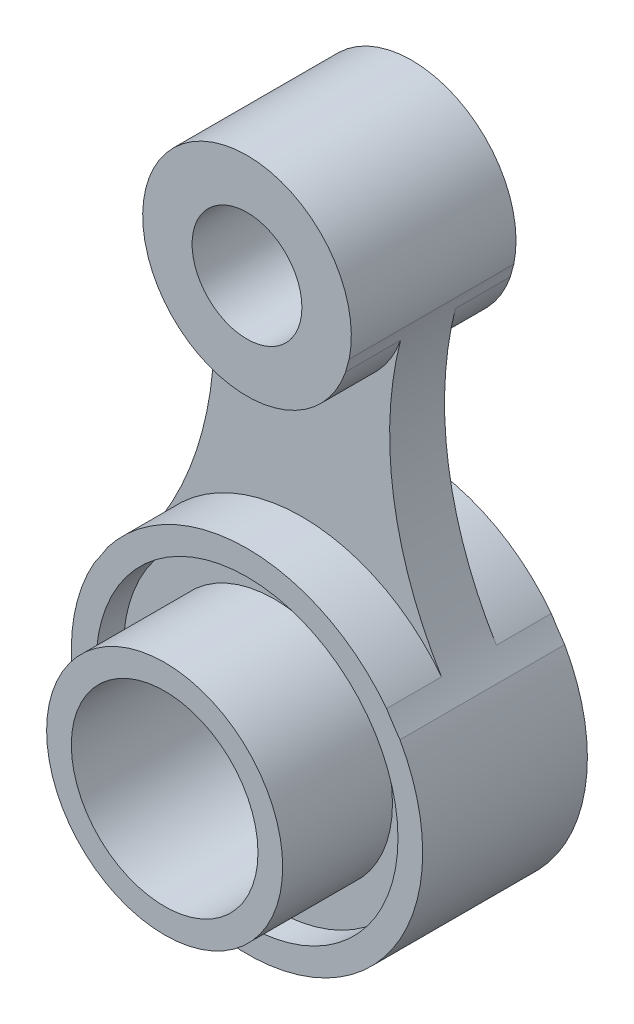
SolidWorks part; units mm, degrees
material "1060 Alloy"
ref_plane "Front Plane" through (0, 0, 0) normal (0, 0, 1) x (1, 0, 0)
ref_plane "Top Plane" through (0, 0, 0) normal (0, 1, 0) x (1, 0, 0)
ref_plane "Right Plane" through (0, 0, 0) normal (1, 0, 0) x (0, 0, -1)
other "Center of Mass"
sketch "Sketch1" plane through (0, 0, 0) normal (0, 0, 1) x (1, 0, 0)
  circle A0 centre (0, 0) radius 32
  circle A1 centre (0, 0) radius 27.5
  circle A2 centre (0, 0) radius 21.5
  circle A3 centre (0, 0) radius 17
  circle A4 centre (0, 75) radius 19
  circle A5 centre (0, 75) radius 10
  arc A8 (-27.8612, 15.7402) -> (-18.6035, 71.1385) centre (-80.2239, 52.9633) ccw
  arc A9 (27.8612, 15.7402) -> (18.6035, 71.1385) centre (80.2239, 52.9633) cw
  point P6 (0, 0)
  point P8 (0, 0)
  point P13 (-18.6035, 71.1385)
extrude "Boss-Extrude6" add sketch "Sketch1" along normal blind 10 contours A0 A9 A4 A8 region at (0, 43.4242, 0)
extrude "Boss-Extrude10" add sketch "Sketch1<11>" along normal blind 20 and the other way blind 10 contours A0 A9 A8 A1 region at (-7.9075, -30.0727, 0)
sketch "Sketch1<11>" plane through (0, 0, 0) normal (0, 0, 1) x (1, 0, 0) same geometry as "Sketch1"
extrude "Boss-Extrude11" add sketch "Sketch1<12>" along normal blind 20 and the other way blind 10 contours A4 A9 A8 A5 region at (0, 56.5374, 0)
sketch "Sketch1<12>" plane through (0, 0, 0) normal (0, 0, 1) x (1, 0, 0) same geometry as "Sketch1"
extrude "Boss-Extrude12" add sketch "Sketch1<13>" along normal blind 15 and the other way blind 10 contours A1 A2 region at (-26.7222, 0, 0)
sketch "Sketch1<13>" plane through (0, 0, 0) normal (0, 0, 1) x (1, 0, 0) same geometry as "Sketch1"
extrude "Boss-Extrude13" add sketch "Sketch1<14>" along normal blind 35 and the other way blind 10 contours A2 A3 region at (-20.8919, 0, 0)
sketch "Sketch1<14>" plane through (0, 0, 0) normal (0, 0, 1) x (1, 0, 0) same geometry as "Sketch1"
